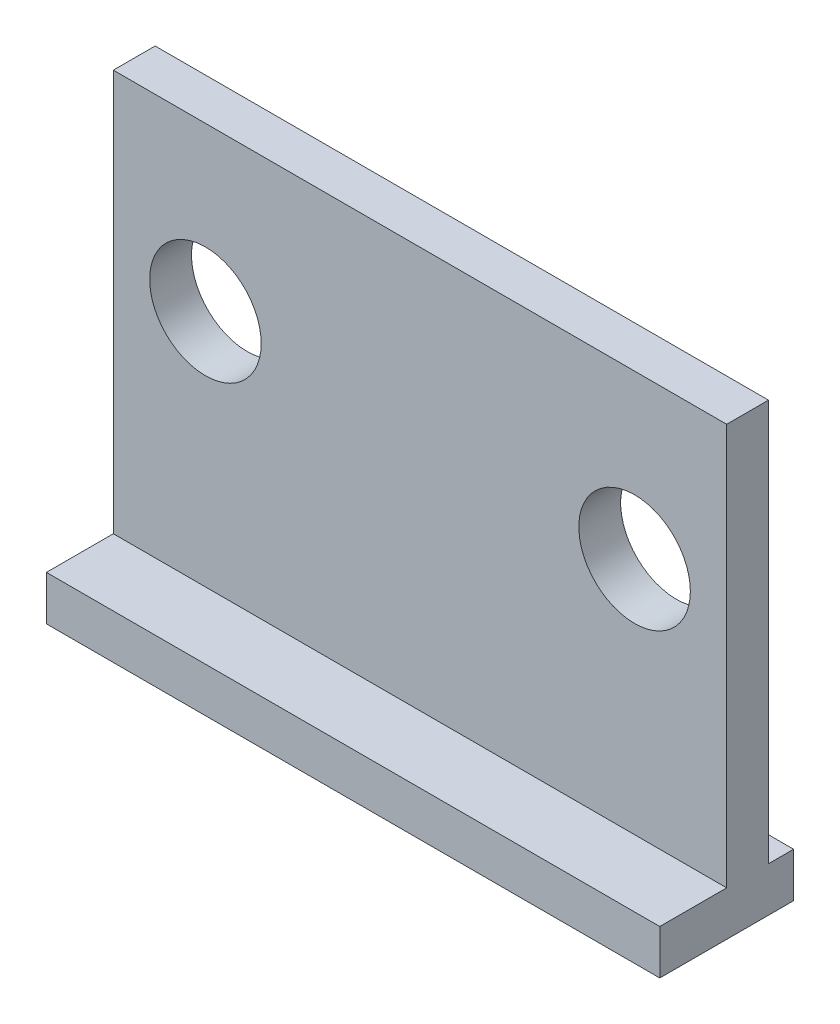
SolidWorks part; units mm, degrees
ref_plane "Front Plane" through (0, 0, 0) normal (0, 0, 1) x (1, 0, 0)
ref_plane "Top Plane" through (0, 0, 0) normal (0, 1, 0) x (1, 0, 0)
ref_plane "Right Plane" through (0, 0, 0) normal (1, 0, 0) x (0, 0, -1)
sketch "Sketch1" plane through (0, 0, 0) normal (0, 0, 1) x (1, 0, 0)
  line L0 (-38.481, 50.8) -> (38.481, 50.8) construction
  line L1 (-55, 0) -> (55, 0)
  line L2 (-55, 0) -> (-55, 80)
  line L3 (-55, 80) -> (55, 80)
  line L4 (55, 0) -> (55, 80)
  line L5 (38.481, 50.8) -> (0, 50.8)
  line L6 (0, 50.8) -> (0, 0) construction
  circle A0 centre (-38.481, 50.8) radius 10
  circle A1 centre (38.481, 50.8) radius 10
  point P4 (0, 0)
  dimension "D4" = 20
  dimension "D5" = 20
  dimension "D1" = 80
  dimension "D2" = 110
  dimension "D3" = 76.962
  dimension "D6" = 50.8
extrude "Boss-Extrude1" add sketch "Sketch1" along normal blind 7.5 contours L1 L4 L3 L2 A1 A0 region at (0, 39.1696, 0)
sketch "Sketch3" plane through (0, 0, 7.5) normal (0, 0, 1) x (1, 0, 0)
  line L0 (55, 0) -> (55, 80) construction
  line L1 (-55, 0) -> (55, 0)
  line L2 (-55, 0) -> (-55, 8)
  line L3 (-55, 8) -> (55, 8)
  line L4 (55, 0) -> (55, 8)
extrude "Boss-Extrude2" add sketch "Sketch3" along normal blind 12 and the other way blind 12
equation "\"shaftDiam\" = 20mm"
equation "\"keyW\" = 8mm"
equation "\"keyL\" = 10mm"
equation "\"clearance\" = .8mm"
equation "\"handleShaftLen\" = 60mm"
equation "\"panelH\" = 80mm"
equation "\"panelW\" = 110mm"
equation "\"D1@Sketch1\"=\"panelH\""
equation "\"D2@Sketch1\"=\"panelW\""
equation "\"D3@Sketch1\"=3.03in"
equation "\"D4@Sketch1\"=\"shaftDiam\""
equation "\"D5@Sketch1\"=\"shaftDiam\""
equation "\"D6@Sketch1\"=4in/2"
equation "\"D1@Boss-Extrude1\"=\"handleShaftLen\"/8"
equation "\"D1@Sketch3\"=\"panelH\"/10"
equation "\"D1@Boss-Extrude2\"=\"handleShaftLen\"/5"
equation "\"D2@Boss-Extrude2\"=\"handleShaftLen\"/5"
